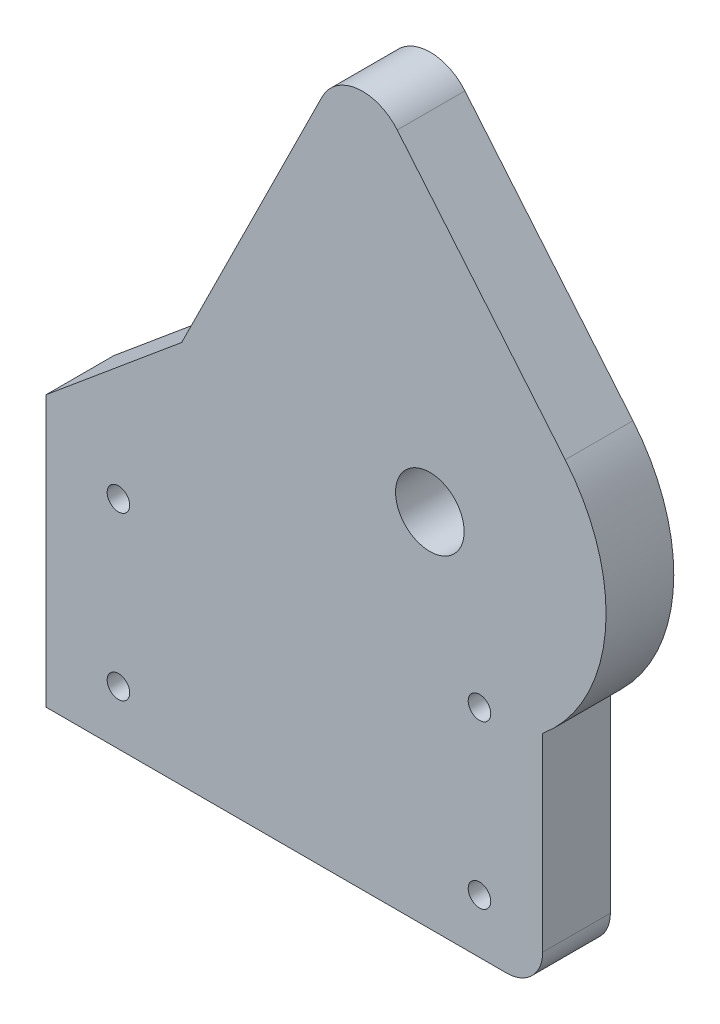
SolidWorks part; units mm, degrees
ref_plane "Front Plane" through (0, 0, 0) normal (0, 0, 1) x (1, 0, 0)
ref_plane "Top Plane" through (0, 0, 0) normal (0, 1, 0) x (1, 0, 0)
ref_plane "Right Plane" through (0, 0, 0) normal (1, 0, 0) x (0, 0, -1)
sketch "Sketch1" plane through (0, 0, 0) normal (0, 0, 1) x (1, 0, 0)
  line L0 (0, 38.1) -> (38.1, 69.85)
  line L1 (0, 0) -> (35.5012, 0)
  line L2 (0, 0) -> (0, 38.1)
  line L5 (19.05, 53.975) -> (38.8216, 93.7987)
  line L6 (49.3874, 95.0401) -> (73.025, 66.675)
  line L8 (38.1, 69.85) -> (69.85, 31.75) construction
  line L9 (35.5012, 0) -> (69.85, 0)
  line L12 (69.85, 0) -> (69.85, 31.75)
  arc A0 (38.1, 69.85) -> (69.85, 31.75) centre (53.975, 50.8) cw
  circle A2 centre (53.975, 50.8) radius 4.826
  circle A3 centre (53.975, 50.8) radius 47.625 construction
  circle A4 centre (44.5092, 90.9749) radius 6.35
  point P0 (0, 0)
  dimension "D6" = 31.75
  dimension "D5" = 0
  dimension "D7" = 9.652
  dimension "D8" = 95.25
  dimension "D9" = 12.7
  dimension "D1" = 38.1
  dimension "D2" = 31.75
  dimension "D3" = 90
  dimension "D4" = 69.85
extrude "Boss-Extrude4" add sketch "Sketch1" along normal blind 9.525 contours L1 L2 | A0 L0 A2 | A4 | A4 L5 L0 | A4 A0 L6 region at (40.084, 33.2843, 0) region at (42.6683, 76.8251, 0) region at (44.5092, 90.9749, 0)
sketch "Sketch2" plane through (0, 0, 9.525) normal (0, 0, 1) x (1, 0, 0)
  line L1 (10.16, 7.62) -> (60.96, 7.62) construction
  line L2 (10.16, 7.62) -> (10.16, 30.48) construction
  line L3 (10.16, 30.48) -> (60.96, 30.48) construction
  line L4 (60.96, 7.62) -> (60.96, 30.48) construction
  line L5 (0, 0) -> (69.85, 0) construction
  line L6 (69.85, 0) -> (69.85, 31.75) construction
  circle A0 centre (10.16, 30.48) radius 1.5875
  circle A1 centre (60.96, 30.48) radius 1.5875
  circle A2 centre (60.96, 7.62) radius 1.5875
  circle A3 centre (10.16, 7.62) radius 1.5875
  dimension "D5" = 3.175
  dimension "D6" = 3.175
  dimension "D7" = 3.175
  dimension "D8" = 3.175
  dimension "D1" = 22.86
  dimension "D2" = 50.8
  dimension "D3" = 8.89
  dimension "D4" = 7.62
extrude "Cut-Extrude2" cut sketch "Sketch2" against normal up to surface (9.525 mm away) contours A0 | A3 | A1 | A2 up to face at (40.8601, 47.6929, 0)
fillet "Fillet1" radius 5.08 1 edges at (69.85, 0, 4.7625)
